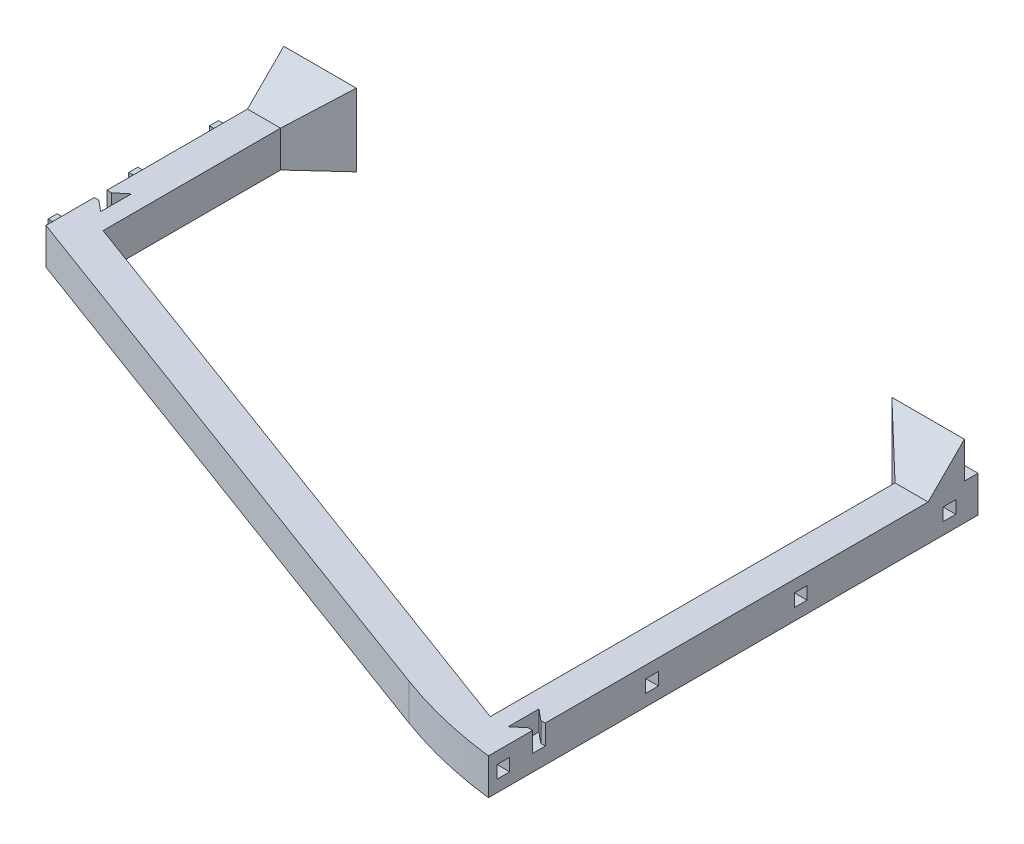
SolidWorks part; units mm, degrees
ref_plane "Přední rovina" through (0, 0, 0) normal (0, 0, 1) x (1, 0, 0)
ref_plane "Horní rovina" through (0, 0, 0) normal (0, 1, 0) x (1, 0, 0)
ref_plane "Pravá rovina" through (0, 0, 0) normal (1, 0, 0) x (0, 0, -1)
sketch "Skica1" plane through (0, 0, 0) normal (0, 1, 0) x (1, 0, 0)
  line L0 (0, 0) -> (0, -111)
  line L1 (0, -111) -> (-150.15, -55.45)
  line L2 (-150.15, -55.45) -> (-150.15, 0)
  line L3 (-150.15, 0) -> (-142.85, 0)
  line L4 (-142.85, 0) -> (-142.85, -50.1539)
  line L5 (-142.85, -50.1539) -> (-7.3, -100.3024)
  line L6 (-7.3, -100.3024) -> (-7.3, 0)
  line L7 (-7.3, 0) -> (0, 0)
  dimension "D1" = 111
  dimension "D2" = 7.3
  dimension "D3" = 7.3
  dimension "D4" = 150.15
  dimension "D5" = 7.5
  dimension "D6" = 55.45
extrude "Přidat vysunutím1" add sketch "Skica1" along normal blind 8
sketch "Skica3" plane through (0, 8, 0) normal (0, 1, 0) x (1, 0, 0)
  line L12 (0, -111) -> (0, 0) construction
  line L13 (-3.4, -93.45) -> (0, -93.45)
  line L14 (-3.4, -93.45) -> (-3.4, -100.25)
  line L15 (-3.4, -100.25) -> (0, -100.25)
  line L16 (0, -93.45) -> (0, -100.25)
  line L17 (0, -95.45) -> (-1, -95.45)
  line L18 (-1, -95.45) -> (-3.4, -93.45)
  line L19 (-3.4, -100.25) -> (-1, -98.25)
  line L20 (-1, -98.25) -> (0, -98.25)
  line L21 (0, -98.25) -> (0, -95.45)
  point P13 (0, 0)
  dimension "D1" = 6.8
  dimension "D2" = 3.4
  dimension "D3" = 2.8
  dimension "D4" = 2
  dimension "D5" = 1
  dimension "D6" = 1
  dimension "D7" = 10.75
extrude "Odebrat vysunutím1" cut sketch "Skica3" against normal blind 4.4 contours L19 L20 L16 L17 L18 L14 region at (-2.0017, 8, 96.85)
sketch "Skica6" plane through (0, 8, 0) normal (0, 1, 0) x (1, 0, 0)
  line L0 (-150.15, 0) -> (-150.15, -55.45) construction
  line L9 (-150.15, -3) -> (-134.15, -3)
  line L10 (-150.15, -3) -> (-150.15, -11)
  line L11 (-150.15, -11) -> (-134.15, -11)
  line L12 (-134.15, -3) -> (-134.15, -11)
  line L13 (-142.85, 0) -> (-150.15, 0) construction
  line L14 (0, -95.45) -> (0, 0) construction
  line L15 (0, -3) -> (-16, -3)
  line L16 (0, -3) -> (0, -11)
  line L17 (0, -11) -> (-16, -11)
  line L18 (-16, -3) -> (-16, -11)
  line L19 (0, 0) -> (-7.3, 0) construction
  dimension "D1" = 3
  dimension "D2" = 16
  dimension "D3" = 3
  dimension "D4" = 8
  dimension "D5" = 16
  dimension "D6" = 8
extrude "Přidat vysunutím3" add sketch "Skica6" against normal blind 16 from offset 8 contours L15 L18 L17 L16 | L9 L12 L11 L10
sketch "Skica8" plane through (0, 0, 0) normal (1, 0, 0) x (0, 0, -1)
  line L3 (-11, 8) -> (-11, 16)
  line L4 (-11, 16) -> (-3, 16)
  line L5 (-3, 16) -> (-11, 8)
extrude "Odebrat vysunutím3" cut sketch "Skica8" against normal through all
sketch "Skica9" plane through (0, 0, 0) normal (0, -1, 0) x (1, 0, 0)
  line L8 (-142.85, 11) -> (-134.15, 11)
  line L9 (-134.15, 11) -> (-134.15, 3)
  line L10 (-134.15, 3) -> (-142.85, 11)
  line L11 (-16, 11) -> (-7.3, 11)
  line L12 (-7.3, 11) -> (-16, 3)
  line L13 (-16, 3) -> (-16, 11)
extrude "Odebrat vysunutím4" cut sketch "Skica9" against normal through all
sketch "Skica4" plane through (0, 0, 0) normal (1, 0, 0) x (0, 0, -1)
  line L0 (-111, 8) -> (-98.25, 8) construction
  line L1 (-106.1, 5.4) -> (-103.3, 5.4)
  line L2 (-106.1, 5.4) -> (-106.1, 2.6)
  line L3 (-106.1, 2.6) -> (-103.3, 2.6)
  line L4 (-103.3, 5.4) -> (-103.3, 2.6)
  line L22 (-73.3, 5.4) -> (-70.5, 5.4)
  line L23 (-73.3, 5.4) -> (-73.3, 2.6)
  line L24 (-73.3, 2.6) -> (-70.5, 2.6)
  line L25 (-70.5, 5.4) -> (-70.5, 2.6)
  line L26 (-40.5, 5.4) -> (-37.7, 5.4)
  line L27 (-40.5, 5.4) -> (-40.5, 2.6)
  line L28 (-40.5, 2.6) -> (-37.7, 2.6)
  line L29 (-37.7, 5.4) -> (-37.7, 2.6)
  line L30 (-7.7, 5.4) -> (-4.9, 5.4)
  line L31 (-7.7, 5.4) -> (-7.7, 2.6)
  line L32 (-7.7, 2.6) -> (-4.9, 2.6)
  line L33 (-4.9, 5.4) -> (-4.9, 2.6)
  line L34 (-3, 8) -> (0, 8) construction
  line L35 (-111, 0) -> (0, 0) construction
  line L37 (0, 8) -> (0, 0) construction
  point P18 (-6.3, 2.6)
  dimension "D1" = 2.8
  dimension "D2" = 2.8
  dimension "D3" = 2.6
  dimension "D4" = 4.9
  dimension "D5" = 2.8
  dimension "D6" = 2.8
  dimension "D7" = 2.6
  dimension "D8" = 30
  dimension "D9" = 30
  dimension "D10" = 2.8
  dimension "D11" = 2.8
  dimension "D12" = 2.6
  dimension "D13" = 2.6
  dimension "D14" = 2.8
  dimension "D15" = 2.8
  dimension "D16" = 30
extrude "Odebrat vysunutím2" cut sketch "Skica4" against normal blind 4.4
sketch "Skica5" plane through (-150.15, 0, 0) normal (-1, 0, 0) x (0, 0, 1)
  line L0 (0, 8) -> (3, 8) construction
  line L1 (13.4, 5) -> (15.4, 5)
  line L2 (13.4, 5) -> (13.4, 3)
  line L3 (13.4, 3) -> (15.4, 3)
  line L4 (15.4, 5) -> (15.4, 3)
  line L5 (31.2, 5) -> (33.2, 5)
  line L6 (31.2, 5) -> (31.2, 3)
  line L7 (31.2, 3) -> (33.2, 3)
  line L8 (33.2, 5) -> (33.2, 3)
  line L9 (0, 8) -> (0, 0) construction
  line L11 (49, 5) -> (51, 5)
  line L12 (49, 5) -> (49, 3)
  line L13 (49, 3) -> (51, 3)
  line L14 (51, 5) -> (51, 3)
  dimension "D1" = 2
  dimension "D2" = 2
  dimension "D3" = 3
  dimension "D4" = 13.4
  dimension "D5" = 15.8
  dimension "D6" = 2
  dimension "D7" = 2
  dimension "D8" = 3
  dimension "D9" = 15.8
  dimension "D10" = 2
  dimension "D11" = 2
  dimension "D12" = 3
extrude "Přidat vysunutím2" add sketch "Skica5" along normal blind 4
sketch "Skica10" plane through (0, 8, 0) normal (0, 1, 0) x (1, 0, 0)
  line L0 (-150.15, -44.8) -> (-149.15, -44.8)
  line L5 (-142.85, 0) -> (-150.15, 0) construction
  line L6 (-150.15, -11) -> (-150.15, -55.45) construction
  line L7 (-150.15, -42) -> (-149.15, -42)
  line L8 (-149.15, -42) -> (-146.75, -40)
  line L9 (-146.75, -40) -> (-146.75, -46.8)
  line L10 (-146.75, -46.8) -> (-149.15, -44.8)
  line L11 (-150.15, -44.8) -> (-150.15, -42)
  dimension "D1" = 6.8
  dimension "D2" = 2.8
  dimension "D3" = 1
  dimension "D4" = 1
  dimension "D5" = 2
  dimension "D6" = 3.4
  dimension "D7" = 40
extrude "Odebrat vysunutím5" cut sketch "Skica10" against normal blind 4.4
sketch "Skica11" plane through (0, 8, 0) normal (0, 1, 0) x (1, 0, 0)
  line L0 (0, -108) -> (-8.1089, -108)
  line L1 (0, -111) -> (0, -98.25) construction
  line L2 (-150.15, -55.45) -> (0, -111) construction
  line L3 (-8.1089, -108) -> (0, -111)
  line L4 (0, -111) -> (0, -108)
  dimension "D1" = 3
extrude "Odebrat vysunutím6" cut sketch "Skica11" against normal through all
fillet "Zaoblit1" radius 100 1 edges at (-8.1089, 4, 108)
